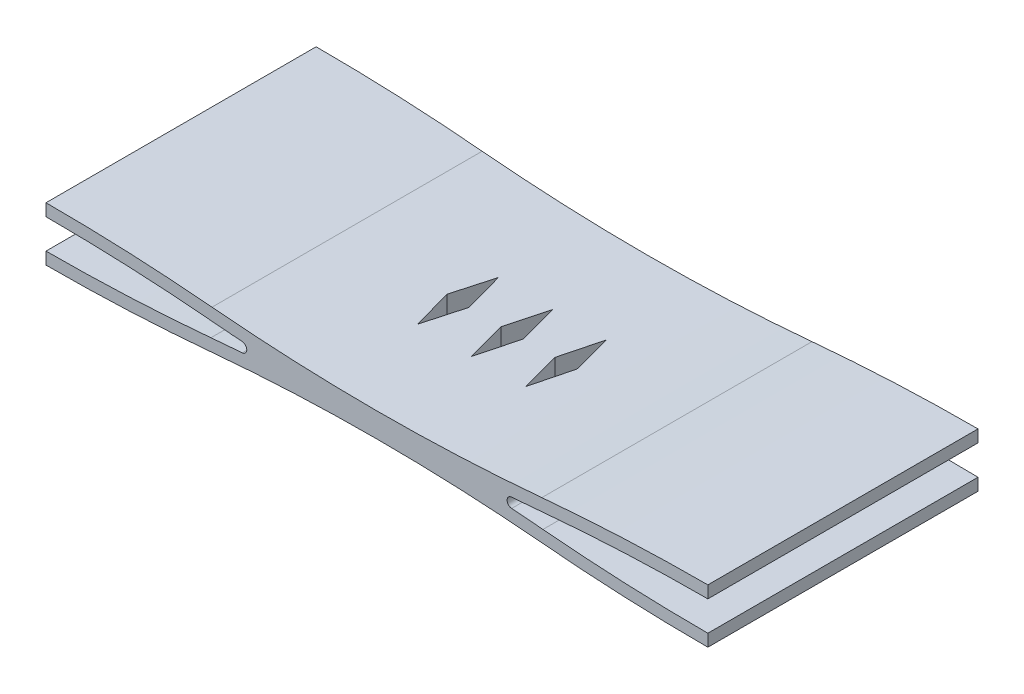
SolidWorks part; units mm, degrees
ref_plane "Front Plane" through (0, 0, 0) normal (0, 0, 1) x (1, 0, 0)
ref_plane "Top Plane" through (0, 0, 0) normal (0, 1, 0) x (1, 0, 0)
ref_plane "Right Plane" through (0, 0, 0) normal (1, 0, 0) x (0, 0, -1)
sketch "Sketch2" plane through (0, 0, 0) normal (0, 0, 1) x (1, 0, 0)
  line L0 (12.25, 0.225) -> (12.25, 0.775) construction
  line L1 (0, 0.225) -> (6.125, 0.5) construction
  line L2 (12.25, 0.775) -> (6.125, 0.5) construction
  line L3 (0, 0.225) -> (12.25, 0.225) construction
  line L4 (12.25, 1) -> (12.25, 0.55)
  line L5 (0, 0.225) -> (0, 6.1586) construction
  line L6 (-12.25, 1) -> (-12.25, 0.55)
  line L7 (0, 0) -> (29.3564, 0) construction
  line L8 (12.25, -1) -> (12.25, -0.55)
  line L9 (-12.25, -1) -> (-12.25, -0.55)
  arc A13 (0, 0.225) -> (6.125, 0.5) centre (0, 68.5727) ccw construction
  arc A15 (12.25, 0.775) -> (6.125, 0.5) centre (12.25, -67.5727) ccw construction
  arc A16 (12.25, 1) -> (6.1048, 0.7241) centre (12.25, -67.5727) ccw
  arc A17 (0, 0.45) -> (6.1048, 0.7241) centre (0, 68.5727) ccw
  arc A18 (12.25, 0.55) -> (6.1452, 0.2759) centre (12.25, -67.5727) ccw
  arc A20 (-4.9868, 0.1816) -> (-6.1452, 0.2759) centre (0, 68.5727) cw
  arc A21 (0, 0.45) -> (-6.1048, 0.7241) centre (0, 68.5727) cw
  arc A22 (-12.25, 0.55) -> (-6.1452, 0.2759) centre (-12.25, -67.5727) cw
  arc A23 (-12.25, 1) -> (-6.1048, 0.7241) centre (-12.25, -67.5727) cw
  arc A24 (4.9868, -0.1816) -> (6.1452, -0.2759) centre (0, -68.5727) cw
  arc A25 (12.25, -0.55) -> (6.1452, -0.2759) centre (12.25, 67.5727) cw
  arc A26 (12.25, -1) -> (6.1048, -0.7241) centre (12.25, 67.5727) cw
  arc A27 (0, -0.45) -> (6.1048, -0.7241) centre (0, -68.5727) cw
  arc A28 (0, -0.45) -> (-6.1048, -0.7241) centre (0, -68.5727) ccw
  arc A29 (-12.25, -1) -> (-6.1048, -0.7241) centre (-12.25, 67.5727) ccw
  arc A30 (-12.25, -0.55) -> (-6.1452, -0.2759) centre (-12.25, 67.5727) ccw
  arc A31 (-4.9868, -0.1816) -> (-6.1452, -0.2759) centre (0, -68.5727) ccw
  arc A32 (4.9868, 0.1816) -> (4.9868, -0.1816) centre (5, 0) ccw
  arc A33 (4.9868, 0.1816) -> (6.1452, 0.2759) centre (0, 68.5727) ccw
  arc A34 (0, 0) -> (6.1452, 0.2759) centre (0, 68.5727) ccw construction
  arc A35 (-4.9868, 0.1816) -> (-4.9868, -0.1816) centre (-5, 0) cw
  dimension "D4" = 24.5
  dimension "D3" = 2
  dimension "D5" = 10
  dimension "D1" = 0.225
  dimension "D2" = 0.225
extrude "Boss-Extrude1" add sketch "Sketch2" along normal blind 10
sketch "Sketch3" plane through (0, 0, 0) normal (0, 1, 0) x (1, 0, 0)
  line L0 (-2, -3.5) -> (-1.5981, -5)
  line L1 (-1.5981, -5) -> (-2, -6.5)
  line L2 (-2, -6.5) -> (-2.4019, -5)
  line L3 (-2.4019, -5) -> (-2, -3.5)
  line L4 (-12.25, -10) -> (-12.25, 0) construction
  line L5 (0, 0) -> (0, -9.167) construction
  point P9 (-12.25, -5)
  dimension "D1" = 30
  dimension "D2" = 3
  dimension "D3" = 2
extrude "Cut-Extrude1" cut sketch "Sketch3" against normal through all both and the other way through all
ref_axis "Axis1" through (-13.475, 0, 0) along (1, 0, 0)
pattern_linear "LPattern1" count 3 spacing 2 along (1, 0, 0) of "Cut-Extrude1"
equation "\"D1@Sketch2\"=\"D2@Sketch2\""
